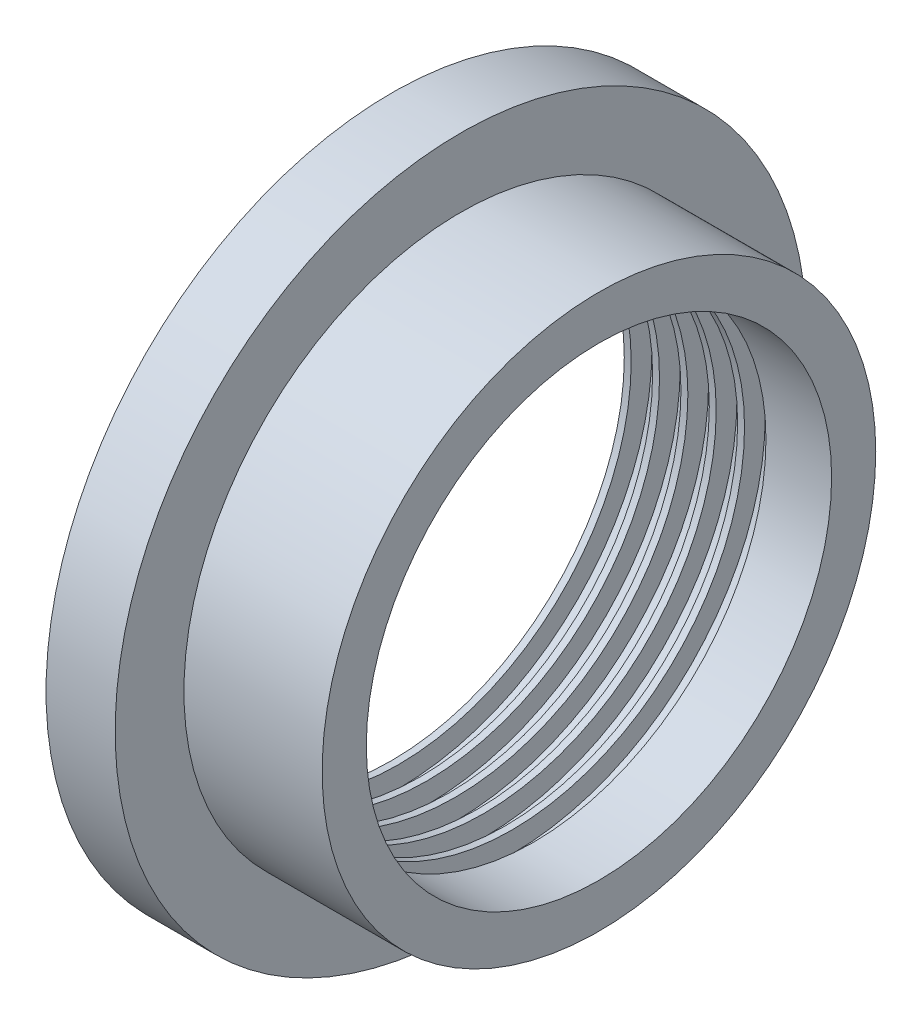
SolidWorks part; units mm, degrees
ref_plane "Front Plane" through (0, 0, 0) normal (0, 0, 1) x (1, 0, 0)
ref_plane "Top Plane" through (0, 0, 0) normal (0, 1, 0) x (1, 0, 0)
ref_plane "Right Plane" through (0, 0, 0) normal (1, 0, 0) x (0, 0, -1)
sketch "Sketch1" plane through (0, 0, 0) normal (0, 0, 1) x (1, 0, 0)
  line L0 (-7.62, 12.7) -> (-7.62, 8.5508)
  line L2 (0, 8.5508) -> (0, 10.1727)
  line L4 (-5.08, 10.1727) -> (-5.08, 12.7)
  line L5 (-5.08, 12.7) -> (-7.62, 12.7)
  line L10 (-7.62, 8.5508) -> (-7.366, 8.5508)
  line L11 (-7.366, 8.5508) -> (-7.366, 9.3128)
  line L12 (-7.366, 9.3128) -> (-6.5786, 9.3128)
  line L13 (-6.5786, 9.3128) -> (-6.5786, 8.5508)
  line L14 (-6.5786, 8.5508) -> (-6.3246, 8.5508)
  line L15 (-6.3246, 8.5508) -> (-6.3246, 9.3128)
  line L16 (-6.3246, 9.3128) -> (-5.5372, 9.3128)
  line L17 (-5.5372, 9.3128) -> (-5.5372, 8.5508)
  line L18 (-5.5372, 8.5508) -> (-5.2832, 8.5508)
  line L19 (-5.2832, 8.5508) -> (-5.2832, 9.3128)
  line L20 (-5.2832, 9.3128) -> (-4.4958, 9.3128)
  line L21 (-4.4958, 9.3128) -> (-4.4958, 8.5508)
  line L22 (-4.4958, 8.5508) -> (-4.2418, 8.5508)
  line L23 (-4.2418, 8.5508) -> (-4.2418, 9.3128)
  line L24 (-4.2418, 9.3128) -> (-3.4544, 9.3128)
  line L25 (-3.4544, 9.3128) -> (-3.4544, 8.5508)
  line L26 (-3.4544, 8.5508) -> (-3.2004, 8.5508)
  line L27 (-3.2004, 8.5508) -> (-3.2004, 9.3128)
  line L28 (-3.2004, 9.3128) -> (-2.413, 9.3128)
  line L29 (-2.413, 9.3128) -> (-2.413, 8.5508)
  line L30 (-2.413, 8.5508) -> (0, 8.5508)
  line L31 (0, 0) -> (-7.2739, 0) construction
  line L33 (-5.08, 10.1727) -> (0, 10.1727)
  line L34 (0, 0) -> (0, 8.5508) construction
  dimension "D1" = 0.7874
  dimension "D2" = 0.254
  dimension "D3" = 0.762
  dimension "D4" = 8.5508
  dimension "D6" = 12.7
  dimension "D5" = 7.62
  dimension "D7" = 10.1727
  dimension "D8" = 2.54
  dimension "D9" = 1.6219
revolve "Revolve1" add sketch "Sketch1" angle 360 about L31
equation "\"Cavity_Depth\" = 0.031in"
equation "\"Cavity_Width\" = 0.031in"
equation "\"D1@Sketch1\"=\"Cavity_Width\""
equation "\"Tooth_Width\" = .01in"
equation "\"D2@Sketch1\"=\"Tooth_Width\""
equation "\"Shaft_Seal_OD\"= 17mm'diameter at seal area"
equation "\"Shaft_clearance\"= .002in"
equation "\"D4@Sketch1\"=\"Shaft_Seal_OD\"/2 +\"Shaft_clearance\""
equation "\"O-Ring_ID\"= .801in"
equation "\"O-Ring_CS\"= .070in"
equation "\"Shaft_OD\"= .5in"
equation "\"D7@Sketch1\"=\"O-Ring_ID\"/2"
